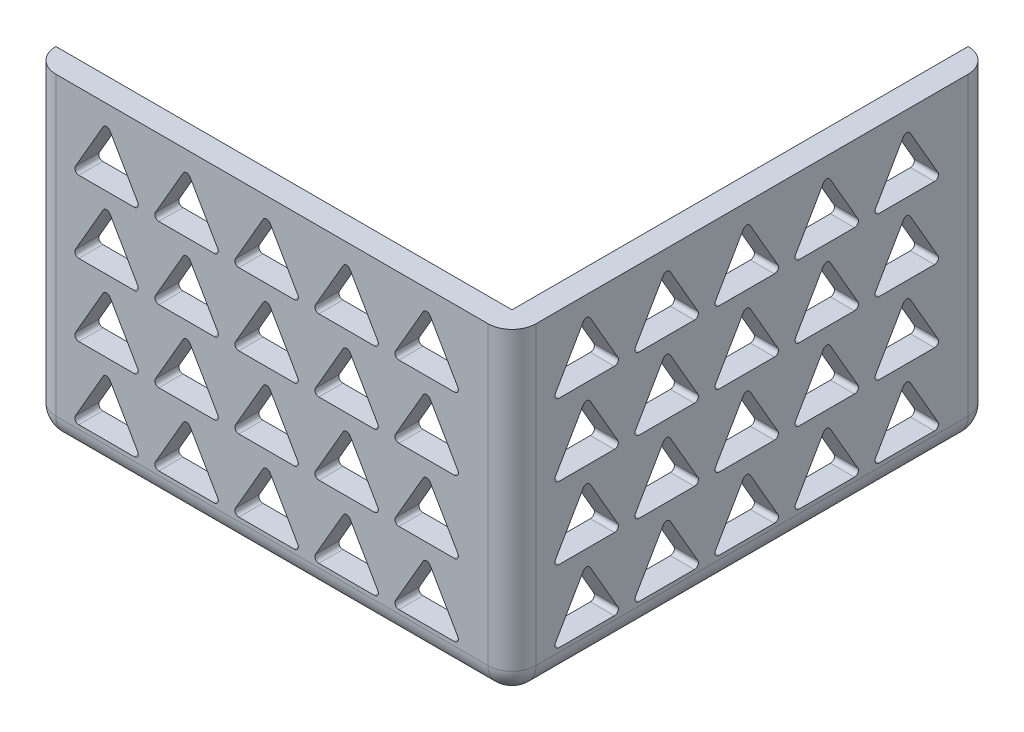
SolidWorks part; units mm, degrees
ref_plane "Front Plane" through (0, 0, 0) normal (0, 0, 1) x (1, 0, 0)
ref_plane "Top Plane" through (0, 0, 0) normal (0, 1, 0) x (1, 0, 0)
ref_plane "Right Plane" through (0, 0, 0) normal (1, 0, 0) x (0, 0, -1)
sketch "Sketch4" plane through (0, 0, 0) normal (0, 0, 1) x (1, 0, 0)
  line L1 (0, 0) -> (152.4, 0)
  line L2 (0, 0) -> (0, -101.6)
  line L3 (0, -101.6) -> (152.4, -101.6)
  line L4 (152.4, 0) -> (152.4, -101.6)
  dimension "D1" = 101.6
  dimension "D2" = 152.4
extrude "Boss-Extrude3" add sketch "Sketch4" along normal blind 152.4
sketch "Sketch5" plane through (0, 0, 0) normal (0, 1, 0) x (1, 0, 0)
  line L0 (152.4, -152.4) -> (0, -152.4) construction
  line L1 (0, 0) -> (144.78, 0)
  line L2 (0, 0) -> (0, -144.78)
  line L3 (0, -144.78) -> (144.78, -144.78)
  line L4 (144.78, 0) -> (144.78, -144.78)
  line L5 (152.4, -152.4) -> (152.4, 0) construction
  dimension "D1" = 7.62
  dimension "D2" = 7.62
extrude "Cut-Extrude1" cut sketch "Sketch5" against normal blind 152.4
fillet "Fillet1" radius 7.62 1 edges at (152.4, -50.8, 152.4)
fillet "Fillet2" radius 7.62 2 edges at (148.59, -101.6, 0) (0, -101.6, 148.59)
fillet "Fillet3" radius 7.62 7 edges at (0, -46.99, 152.4) (2.2318, -99.3682, 152.4) (152.4, -46.99, 0) (152.4, -99.3682, 2.2318) (152.4, -101.6, 76.2) (150.1682, -101.6, 150.1682) (76.2, -101.6, 152.4)
sketch "Sketch6" plane through (0, 0, 152.4) normal (0, 0, 1) x (1, 0, 0)
  line L0 (144.78, 0) -> (7.62, 0) construction
  line L1 (22.5987, -6.985) -> (13.7999, -22.225)
  line L2 (14.8997, -24.13) -> (32.4973, -24.13)
  line L3 (33.5972, -22.225) -> (24.7984, -6.985)
  line L4 (7.62, 0) -> (7.62, -93.98) construction
  line L5 (58.9972, -22.225) -> (50.1984, -6.985)
  line L6 (40.2997, -24.13) -> (57.8973, -24.13)
  line L7 (47.9987, -6.985) -> (39.1999, -22.225)
  line L8 (84.3972, -22.225) -> (75.5984, -6.985)
  line L9 (65.6997, -24.13) -> (83.2973, -24.13)
  line L10 (73.3987, -6.985) -> (64.5999, -22.225)
  line L11 (109.7972, -22.225) -> (100.9984, -6.985)
  line L12 (91.0997, -24.13) -> (108.6973, -24.13)
  line L13 (98.7987, -6.985) -> (89.9999, -22.225)
  line L14 (135.1972, -22.225) -> (126.3984, -6.985)
  line L15 (116.4997, -24.13) -> (134.0973, -24.13)
  line L16 (124.1987, -6.985) -> (115.3999, -22.225)
  line L17 (22.5987, -29.845) -> (13.7999, -45.085)
  line L18 (14.8997, -46.99) -> (32.4973, -46.99)
  line L19 (33.5972, -45.085) -> (24.7984, -29.845)
  line L20 (47.9987, -29.845) -> (39.1999, -45.085)
  line L21 (58.9972, -45.085) -> (50.1984, -29.845)
  line L22 (40.2997, -46.99) -> (57.8973, -46.99)
  line L23 (65.6997, -46.99) -> (83.2973, -46.99)
  line L24 (84.3972, -45.085) -> (75.5984, -29.845)
  line L25 (73.3987, -29.845) -> (64.5999, -45.085)
  line L26 (98.7987, -29.845) -> (89.9999, -45.085)
  line L27 (91.0997, -46.99) -> (108.6973, -46.99)
  line L28 (109.7972, -45.085) -> (100.9984, -29.845)
  line L29 (124.1987, -29.845) -> (115.3999, -45.085)
  line L30 (116.4997, -46.99) -> (134.0973, -46.99)
  line L31 (135.1972, -45.085) -> (126.3984, -29.845)
  line L32 (22.5987, -52.705) -> (13.7999, -67.945)
  line L33 (14.8997, -69.85) -> (32.4973, -69.85)
  line L34 (33.5972, -67.945) -> (24.7984, -52.705)
  line L35 (47.9987, -52.705) -> (39.1999, -67.945)
  line L36 (58.9972, -67.945) -> (50.1984, -52.705)
  line L37 (40.2997, -69.85) -> (57.8973, -69.85)
  line L38 (65.6997, -69.85) -> (83.2973, -69.85)
  line L39 (84.3972, -67.945) -> (75.5984, -52.705)
  line L40 (73.3987, -52.705) -> (64.5999, -67.945)
  line L41 (98.7987, -52.705) -> (89.9999, -67.945)
  line L42 (91.0997, -69.85) -> (108.6973, -69.85)
  line L43 (109.7972, -67.945) -> (100.9984, -52.705)
  line L44 (124.1987, -52.705) -> (115.3999, -67.945)
  line L45 (116.4997, -69.85) -> (134.0973, -69.85)
  line L46 (135.1972, -67.945) -> (126.3984, -52.705)
  line L47 (22.5987, -75.565) -> (13.7999, -90.805)
  line L48 (14.8997, -92.71) -> (32.4973, -92.71)
  line L49 (33.5972, -90.805) -> (24.7984, -75.565)
  line L50 (47.9987, -75.565) -> (39.1999, -90.805)
  line L51 (58.9972, -90.805) -> (50.1984, -75.565)
  line L52 (40.2997, -92.71) -> (57.8973, -92.71)
  line L53 (65.6997, -92.71) -> (83.2973, -92.71)
  line L54 (84.3972, -90.805) -> (75.5984, -75.565)
  line L55 (73.3987, -75.565) -> (64.5999, -90.805)
  line L56 (98.7987, -75.565) -> (89.9999, -90.805)
  line L57 (91.0997, -92.71) -> (108.6973, -92.71)
  line L58 (109.7972, -90.805) -> (100.9984, -75.565)
  line L59 (124.1987, -75.565) -> (115.3999, -90.805)
  line L60 (116.4997, -92.71) -> (134.0973, -92.71)
  line L61 (135.1972, -90.805) -> (126.3984, -75.565)
  circle A0 centre (23.6985, -17.78) radius 6.35 construction
  arc A1 (13.7999, -22.225) -> (14.8997, -24.13) centre (14.8997, -22.86) ccw
  arc A2 (32.4973, -24.13) -> (33.5972, -22.225) centre (32.4973, -22.86) ccw
  arc A3 (22.5987, -6.985) -> (24.7984, -6.985) centre (23.6985, -7.62) cw
  arc A4 (57.8973, -24.13) -> (58.9972, -22.225) centre (57.8973, -22.86) ccw
  arc A5 (47.9987, -6.985) -> (50.1984, -6.985) centre (49.0985, -7.62) cw
  arc A6 (39.1999, -22.225) -> (40.2997, -24.13) centre (40.2997, -22.86) ccw
  arc A7 (83.2973, -24.13) -> (84.3972, -22.225) centre (83.2973, -22.86) ccw
  arc A8 (73.3987, -6.985) -> (75.5984, -6.985) centre (74.4985, -7.62) cw
  arc A9 (64.5999, -22.225) -> (65.6997, -24.13) centre (65.6997, -22.86) ccw
  arc A10 (108.6973, -24.13) -> (109.7972, -22.225) centre (108.6973, -22.86) ccw
  arc A11 (98.7987, -6.985) -> (100.9984, -6.985) centre (99.8985, -7.62) cw
  arc A12 (89.9999, -22.225) -> (91.0997, -24.13) centre (91.0997, -22.86) ccw
  arc A13 (134.0973, -24.13) -> (135.1972, -22.225) centre (134.0973, -22.86) ccw
  arc A14 (124.1987, -6.985) -> (126.3984, -6.985) centre (125.2985, -7.62) cw
  arc A15 (115.3999, -22.225) -> (116.4997, -24.13) centre (116.4997, -22.86) ccw
  arc A16 (32.4973, -46.99) -> (33.5972, -45.085) centre (32.4973, -45.72) ccw
  arc A17 (13.7999, -45.085) -> (14.8997, -46.99) centre (14.8997, -45.72) ccw
  arc A18 (22.5987, -29.845) -> (24.7984, -29.845) centre (23.6985, -30.48) cw
  arc A19 (47.9987, -29.845) -> (50.1984, -29.845) centre (49.0985, -30.48) cw
  arc A20 (57.8973, -46.99) -> (58.9972, -45.085) centre (57.8973, -45.72) ccw
  arc A21 (39.1999, -45.085) -> (40.2997, -46.99) centre (40.2997, -45.72) ccw
  arc A22 (64.5999, -45.085) -> (65.6997, -46.99) centre (65.6997, -45.72) ccw
  arc A23 (83.2973, -46.99) -> (84.3972, -45.085) centre (83.2973, -45.72) ccw
  arc A24 (73.3987, -29.845) -> (75.5984, -29.845) centre (74.4985, -30.48) cw
  arc A25 (89.9999, -45.085) -> (91.0997, -46.99) centre (91.0997, -45.72) ccw
  arc A26 (108.6973, -46.99) -> (109.7972, -45.085) centre (108.6973, -45.72) ccw
  arc A27 (98.7987, -29.845) -> (100.9984, -29.845) centre (99.8985, -30.48) cw
  arc A28 (124.1987, -29.845) -> (126.3984, -29.845) centre (125.2985, -30.48) cw
  arc A29 (115.3999, -45.085) -> (116.4997, -46.99) centre (116.4997, -45.72) ccw
  arc A30 (134.0973, -46.99) -> (135.1972, -45.085) centre (134.0973, -45.72) ccw
  arc A31 (32.4973, -69.85) -> (33.5972, -67.945) centre (32.4973, -68.58) ccw
  arc A32 (13.7999, -67.945) -> (14.8997, -69.85) centre (14.8997, -68.58) ccw
  arc A33 (22.5987, -52.705) -> (24.7984, -52.705) centre (23.6985, -53.34) cw
  arc A34 (47.9987, -52.705) -> (50.1984, -52.705) centre (49.0985, -53.34) cw
  arc A35 (57.8973, -69.85) -> (58.9972, -67.945) centre (57.8973, -68.58) ccw
  arc A36 (39.1999, -67.945) -> (40.2997, -69.85) centre (40.2997, -68.58) ccw
  arc A37 (64.5999, -67.945) -> (65.6997, -69.85) centre (65.6997, -68.58) ccw
  arc A38 (83.2973, -69.85) -> (84.3972, -67.945) centre (83.2973, -68.58) ccw
  arc A39 (73.3987, -52.705) -> (75.5984, -52.705) centre (74.4985, -53.34) cw
  arc A40 (89.9999, -67.945) -> (91.0997, -69.85) centre (91.0997, -68.58) ccw
  arc A41 (108.6973, -69.85) -> (109.7972, -67.945) centre (108.6973, -68.58) ccw
  arc A42 (98.7987, -52.705) -> (100.9984, -52.705) centre (99.8985, -53.34) cw
  arc A43 (124.1987, -52.705) -> (126.3984, -52.705) centre (125.2985, -53.34) cw
  arc A44 (115.3999, -67.945) -> (116.4997, -69.85) centre (116.4997, -68.58) ccw
  arc A45 (134.0973, -69.85) -> (135.1972, -67.945) centre (134.0973, -68.58) ccw
  arc A46 (32.4973, -92.71) -> (33.5972, -90.805) centre (32.4973, -91.44) ccw
  arc A47 (13.7999, -90.805) -> (14.8997, -92.71) centre (14.8997, -91.44) ccw
  arc A48 (22.5987, -75.565) -> (24.7984, -75.565) centre (23.6985, -76.2) cw
  arc A49 (47.9987, -75.565) -> (50.1984, -75.565) centre (49.0985, -76.2) cw
  arc A50 (57.8973, -92.71) -> (58.9972, -90.805) centre (57.8973, -91.44) ccw
  arc A51 (39.1999, -90.805) -> (40.2997, -92.71) centre (40.2997, -91.44) ccw
  arc A52 (64.5999, -90.805) -> (65.6997, -92.71) centre (65.6997, -91.44) ccw
  arc A53 (83.2973, -92.71) -> (84.3972, -90.805) centre (83.2973, -91.44) ccw
  arc A54 (73.3987, -75.565) -> (75.5984, -75.565) centre (74.4985, -76.2) cw
  arc A55 (89.9999, -90.805) -> (91.0997, -92.71) centre (91.0997, -91.44) ccw
  arc A56 (108.6973, -92.71) -> (109.7972, -90.805) centre (108.6973, -91.44) ccw
  arc A57 (98.7987, -75.565) -> (100.9984, -75.565) centre (99.8985, -76.2) cw
  arc A58 (124.1987, -75.565) -> (126.3984, -75.565) centre (125.2985, -76.2) cw
  arc A59 (115.3999, -90.805) -> (116.4997, -92.71) centre (116.4997, -91.44) ccw
  arc A60 (134.0973, -92.71) -> (135.1972, -90.805) centre (134.0973, -91.44) ccw
  point P11 (12.7, -24.13)
  point P16 (23.6985, -5.08)
  dimension "D2" = 12.7
  dimension "D4" = 1.27
  dimension "D1" = 5.08
  dimension "D3" = 5.08
  dimension "D5" = 5
  dimension "D6" = 4
extrude "Cut-Extrude2" cut sketch "Sketch6" against normal blind 7.62
sketch "Sketch7" plane through (152.4, 0, 0) normal (1, 0, 0) x (0, 0, -1)
  line L0 (-144.78, 0) -> (-7.62, 0) construction
  line L1 (-129.8013, -6.985) -> (-138.6001, -22.225)
  line L2 (-137.5003, -24.13) -> (-119.9027, -24.13)
  line L3 (-118.8028, -22.225) -> (-127.6016, -6.985)
  line L4 (-144.78, 0) -> (-144.78, -93.98) construction
  line L5 (-112.1003, -24.13) -> (-94.5027, -24.13)
  line L6 (-93.4028, -22.225) -> (-102.2016, -6.985)
  line L7 (-104.4013, -6.985) -> (-113.2001, -22.225)
  line L8 (-86.7003, -24.13) -> (-69.1027, -24.13)
  line L9 (-68.0028, -22.225) -> (-76.8016, -6.985)
  line L10 (-79.0013, -6.985) -> (-87.8001, -22.225)
  line L11 (-61.3003, -24.13) -> (-43.7027, -24.13)
  line L12 (-42.6028, -22.225) -> (-51.4016, -6.985)
  line L13 (-53.6013, -6.985) -> (-62.4001, -22.225)
  line L14 (-35.9003, -24.13) -> (-18.3027, -24.13)
  line L15 (-17.2028, -22.225) -> (-26.0016, -6.985)
  line L16 (-28.2013, -6.985) -> (-37.0001, -22.225)
  line L17 (-35.9003, -46.99) -> (-18.3027, -46.99)
  line L18 (-17.2028, -45.085) -> (-26.0016, -29.845)
  line L19 (-28.2013, -29.845) -> (-37.0001, -45.085)
  line L20 (-61.3003, -46.99) -> (-43.7027, -46.99)
  line L21 (-42.6028, -45.085) -> (-51.4016, -29.845)
  line L22 (-53.6013, -29.845) -> (-62.4001, -45.085)
  line L23 (-86.7003, -46.99) -> (-69.1027, -46.99)
  line L24 (-68.0028, -45.085) -> (-76.8016, -29.845)
  line L25 (-79.0013, -29.845) -> (-87.8001, -45.085)
  line L26 (-112.1003, -46.99) -> (-94.5027, -46.99)
  line L27 (-93.4028, -45.085) -> (-102.2016, -29.845)
  line L28 (-104.4013, -29.845) -> (-113.2001, -45.085)
  line L29 (-137.5003, -46.99) -> (-119.9027, -46.99)
  line L30 (-118.8028, -45.085) -> (-127.6016, -29.845)
  line L31 (-129.8013, -29.845) -> (-138.6001, -45.085)
  line L32 (-35.9003, -69.85) -> (-18.3027, -69.85)
  line L33 (-17.2028, -67.945) -> (-26.0016, -52.705)
  line L34 (-28.2013, -52.705) -> (-37.0001, -67.945)
  line L35 (-61.3003, -69.85) -> (-43.7027, -69.85)
  line L36 (-42.6028, -67.945) -> (-51.4016, -52.705)
  line L37 (-53.6013, -52.705) -> (-62.4001, -67.945)
  line L38 (-86.7003, -69.85) -> (-69.1027, -69.85)
  line L39 (-68.0028, -67.945) -> (-76.8016, -52.705)
  line L40 (-79.0013, -52.705) -> (-87.8001, -67.945)
  line L41 (-112.1003, -69.85) -> (-94.5027, -69.85)
  line L42 (-93.4028, -67.945) -> (-102.2016, -52.705)
  line L43 (-104.4013, -52.705) -> (-113.2001, -67.945)
  line L44 (-137.5003, -69.85) -> (-119.9027, -69.85)
  line L45 (-118.8028, -67.945) -> (-127.6016, -52.705)
  line L46 (-129.8013, -52.705) -> (-138.6001, -67.945)
  line L47 (-35.9003, -92.71) -> (-18.3027, -92.71)
  line L48 (-17.2028, -90.805) -> (-26.0016, -75.565)
  line L49 (-28.2013, -75.565) -> (-37.0001, -90.805)
  line L50 (-61.3003, -92.71) -> (-43.7027, -92.71)
  line L51 (-42.6028, -90.805) -> (-51.4016, -75.565)
  line L52 (-53.6013, -75.565) -> (-62.4001, -90.805)
  line L53 (-86.7003, -92.71) -> (-69.1027, -92.71)
  line L54 (-68.0028, -90.805) -> (-76.8016, -75.565)
  line L55 (-79.0013, -75.565) -> (-87.8001, -90.805)
  line L56 (-112.1003, -92.71) -> (-94.5027, -92.71)
  line L57 (-93.4028, -90.805) -> (-102.2016, -75.565)
  line L58 (-104.4013, -75.565) -> (-113.2001, -90.805)
  line L59 (-137.5003, -92.71) -> (-119.9027, -92.71)
  line L60 (-118.8028, -90.805) -> (-127.6016, -75.565)
  line L61 (-129.8013, -75.565) -> (-138.6001, -90.805)
  circle A0 centre (-128.7015, -17.78) radius 6.35 construction
  arc A1 (-138.6001, -22.225) -> (-137.5003, -24.13) centre (-137.5003, -22.86) ccw
  arc A2 (-119.9027, -24.13) -> (-118.8028, -22.225) centre (-119.9027, -22.86) ccw
  arc A3 (-129.8013, -6.985) -> (-127.6016, -6.985) centre (-128.7015, -7.62) cw
  arc A4 (-94.5027, -24.13) -> (-93.4028, -22.225) centre (-94.5027, -22.86) ccw
  arc A5 (-104.4013, -6.985) -> (-102.2016, -6.985) centre (-103.3015, -7.62) cw
  arc A6 (-113.2001, -22.225) -> (-112.1003, -24.13) centre (-112.1003, -22.86) ccw
  arc A7 (-69.1027, -24.13) -> (-68.0028, -22.225) centre (-69.1027, -22.86) ccw
  arc A8 (-79.0013, -6.985) -> (-76.8016, -6.985) centre (-77.9015, -7.62) cw
  arc A9 (-87.8001, -22.225) -> (-86.7003, -24.13) centre (-86.7003, -22.86) ccw
  arc A10 (-43.7027, -24.13) -> (-42.6028, -22.225) centre (-43.7027, -22.86) ccw
  arc A11 (-53.6013, -6.985) -> (-51.4016, -6.985) centre (-52.5015, -7.62) cw
  arc A12 (-62.4001, -22.225) -> (-61.3003, -24.13) centre (-61.3003, -22.86) ccw
  arc A13 (-18.3027, -24.13) -> (-17.2028, -22.225) centre (-18.3027, -22.86) ccw
  arc A14 (-28.2013, -6.985) -> (-26.0016, -6.985) centre (-27.1015, -7.62) cw
  arc A15 (-37.0001, -22.225) -> (-35.9003, -24.13) centre (-35.9003, -22.86) ccw
  arc A16 (-18.3027, -46.99) -> (-17.2028, -45.085) centre (-18.3027, -45.72) ccw
  arc A17 (-28.2013, -29.845) -> (-26.0016, -29.845) centre (-27.1015, -30.48) cw
  arc A18 (-37.0001, -45.085) -> (-35.9003, -46.99) centre (-35.9003, -45.72) ccw
  arc A19 (-62.4001, -45.085) -> (-61.3003, -46.99) centre (-61.3003, -45.72) ccw
  arc A20 (-43.7027, -46.99) -> (-42.6028, -45.085) centre (-43.7027, -45.72) ccw
  arc A21 (-53.6013, -29.845) -> (-51.4016, -29.845) centre (-52.5015, -30.48) cw
  arc A22 (-69.1027, -46.99) -> (-68.0028, -45.085) centre (-69.1027, -45.72) ccw
  arc A23 (-79.0013, -29.845) -> (-76.8016, -29.845) centre (-77.9015, -30.48) cw
  arc A24 (-87.8001, -45.085) -> (-86.7003, -46.99) centre (-86.7003, -45.72) ccw
  arc A25 (-94.5027, -46.99) -> (-93.4028, -45.085) centre (-94.5027, -45.72) ccw
  arc A26 (-104.4013, -29.845) -> (-102.2016, -29.845) centre (-103.3015, -30.48) cw
  arc A27 (-113.2001, -45.085) -> (-112.1003, -46.99) centre (-112.1003, -45.72) ccw
  arc A28 (-119.9027, -46.99) -> (-118.8028, -45.085) centre (-119.9027, -45.72) ccw
  arc A29 (-129.8013, -29.845) -> (-127.6016, -29.845) centre (-128.7015, -30.48) cw
  arc A30 (-138.6001, -45.085) -> (-137.5003, -46.99) centre (-137.5003, -45.72) ccw
  arc A31 (-18.3027, -69.85) -> (-17.2028, -67.945) centre (-18.3027, -68.58) ccw
  arc A32 (-28.2013, -52.705) -> (-26.0016, -52.705) centre (-27.1015, -53.34) cw
  arc A33 (-37.0001, -67.945) -> (-35.9003, -69.85) centre (-35.9003, -68.58) ccw
  arc A34 (-62.4001, -67.945) -> (-61.3003, -69.85) centre (-61.3003, -68.58) ccw
  arc A35 (-43.7027, -69.85) -> (-42.6028, -67.945) centre (-43.7027, -68.58) ccw
  arc A36 (-53.6013, -52.705) -> (-51.4016, -52.705) centre (-52.5015, -53.34) cw
  arc A37 (-69.1027, -69.85) -> (-68.0028, -67.945) centre (-69.1027, -68.58) ccw
  arc A38 (-79.0013, -52.705) -> (-76.8016, -52.705) centre (-77.9015, -53.34) cw
  arc A39 (-87.8001, -67.945) -> (-86.7003, -69.85) centre (-86.7003, -68.58) ccw
  arc A40 (-94.5027, -69.85) -> (-93.4028, -67.945) centre (-94.5027, -68.58) ccw
  arc A41 (-104.4013, -52.705) -> (-102.2016, -52.705) centre (-103.3015, -53.34) cw
  arc A42 (-113.2001, -67.945) -> (-112.1003, -69.85) centre (-112.1003, -68.58) ccw
  arc A43 (-119.9027, -69.85) -> (-118.8028, -67.945) centre (-119.9027, -68.58) ccw
  arc A44 (-129.8013, -52.705) -> (-127.6016, -52.705) centre (-128.7015, -53.34) cw
  arc A45 (-138.6001, -67.945) -> (-137.5003, -69.85) centre (-137.5003, -68.58) ccw
  arc A46 (-18.3027, -92.71) -> (-17.2028, -90.805) centre (-18.3027, -91.44) ccw
  arc A47 (-28.2013, -75.565) -> (-26.0016, -75.565) centre (-27.1015, -76.2) cw
  arc A48 (-37.0001, -90.805) -> (-35.9003, -92.71) centre (-35.9003, -91.44) ccw
  arc A49 (-62.4001, -90.805) -> (-61.3003, -92.71) centre (-61.3003, -91.44) ccw
  arc A50 (-43.7027, -92.71) -> (-42.6028, -90.805) centre (-43.7027, -91.44) ccw
  arc A51 (-53.6013, -75.565) -> (-51.4016, -75.565) centre (-52.5015, -76.2) cw
  arc A52 (-69.1027, -92.71) -> (-68.0028, -90.805) centre (-69.1027, -91.44) ccw
  arc A53 (-79.0013, -75.565) -> (-76.8016, -75.565) centre (-77.9015, -76.2) cw
  arc A54 (-87.8001, -90.805) -> (-86.7003, -92.71) centre (-86.7003, -91.44) ccw
  arc A55 (-94.5027, -92.71) -> (-93.4028, -90.805) centre (-94.5027, -91.44) ccw
  arc A56 (-104.4013, -75.565) -> (-102.2016, -75.565) centre (-103.3015, -76.2) cw
  arc A57 (-113.2001, -90.805) -> (-112.1003, -92.71) centre (-112.1003, -91.44) ccw
  arc A58 (-119.9027, -92.71) -> (-118.8028, -90.805) centre (-119.9027, -91.44) ccw
  arc A59 (-129.8013, -75.565) -> (-127.6016, -75.565) centre (-128.7015, -76.2) cw
  arc A60 (-138.6001, -90.805) -> (-137.5003, -92.71) centre (-137.5003, -91.44) ccw
  point P11 (-139.7, -24.13)
  point P16 (-128.7015, -5.08)
  dimension "D3" = 1.27
  dimension "D1" = 5.08
  dimension "D2" = 5.08
  dimension "D4" = 5
  dimension "D5" = 4
extrude "Cut-Extrude3" cut sketch "Sketch7" against normal blind 7.62
